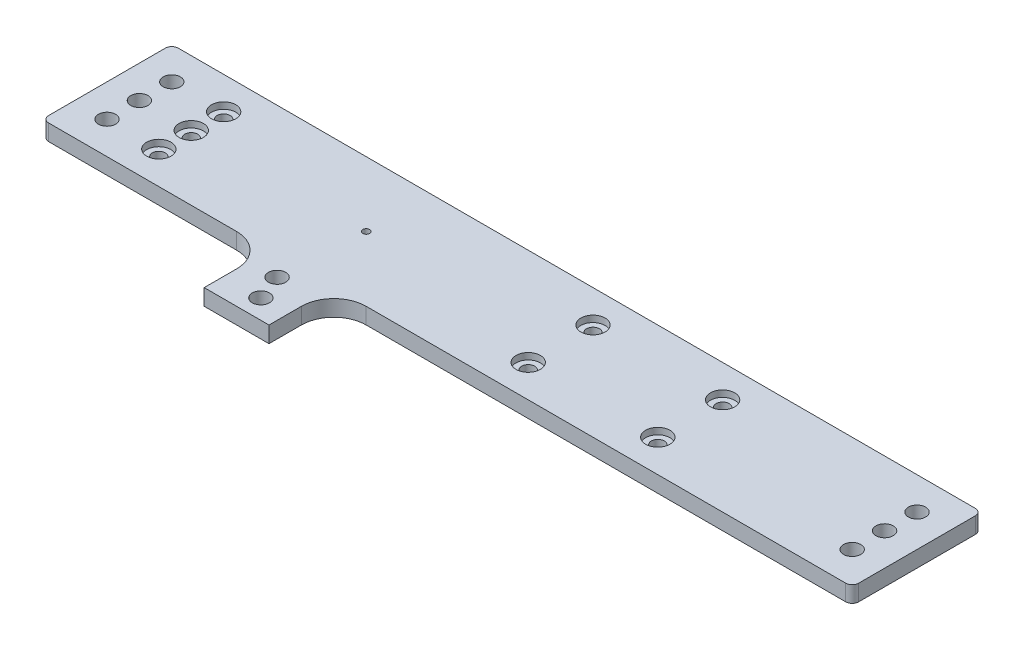
SolidWorks part; units mm, degrees
material "6061-T6 (SS)"
ref_plane "Front" through (0, 0, 0) normal (0, 0, 1) x (1, 0, 0)
ref_plane "Top" through (0, 0, 0) normal (0, 1, 0) x (1, 0, 0)
ref_plane "Right" through (0, 0, 0) normal (1, 0, 0) x (0, 0, -1)
sketch "Sketch1" plane through (0, 0, 0) normal (0, 1, 0) x (1, 0, 0)
  line L1 (-158.75, -25.4) -> (158.75, -25.4)
  line L2 (-158.75, -25.4) -> (-158.75, 25.4)
  line L3 (-158.75, 25.4) -> (158.75, 25.4)
  line L4 (158.75, -25.4) -> (158.75, 25.4)
  line L5 (-158.75, -25.4) -> (158.75, 25.4) construction
  line L6 (-158.75, 25.4) -> (158.75, -25.4) construction
  point P0 (0, 0)
  dimension "D1" = 50.8
  dimension "D2" = 317.5
extrude "Boss-Extrude1" add sketch "Sketch1" along normal blind 6.35
hole_wizard "CBORE for #10 Socket Head Cap Screw1" positions "Sketch2" profile "Sketch4" counterbore size "#10" standard "ANSI Inch" end condition through all
sketch "Sketch2" plane through (0, 6.35, 0) normal (0, 1, 0) x (1, 0, 0)
  line L2 (158.75, 25.4) -> (-158.75, 25.4) construction
  line L6 (-158.75, -25.4) -> (158.75, -25.4) construction
  line L8 (-158.75, 25.4) -> (-158.75, -25.4) construction
  line L12 (158.75, -25.4) -> (158.75, 25.4) construction
  line L15 (19.05, 12.7) -> (19.05, 25.4) construction
  line L17 (19.05, -12.7) -> (19.05, -25.4) construction
  line L18 (-125.73, -25.4) -> (-125.73, -12.7) construction
  line L20 (-125.73, 0) -> (-125.73, 12.7) construction
  line L21 (-125.73, 12.7) -> (-125.73, 25.4) construction
  line L22 (-125.73, 0) -> (-125.73, -12.7) construction
  point P64 (19.05, 12.7)
  point P66 (69.85, 12.7)
  point P68 (19.05, -12.7)
  point P70 (69.85, -12.7)
  point P92 (-125.73, 12.7)
  point P94 (-125.73, 0)
  point P102 (-125.73, -12.7)
  dimension "D2" = 50.8
  dimension "D3" = 25.4
  dimension "D4" = 88.9
  dimension "D5" = 33.02
sketch "Sketch4" plane through (-125.73, 6.35, 12.7) normal (1, 0, 0) x (0, 0, 1)
  line L0 (0, 0) -> (0, 6.35)
  line L1 (0, 6.35) -> (2.5527, 6.35)
  line L3 (2.5527, 6.35) -> (2.5527, 2.54)
  line L4 (2.5527, 2.54) -> (4.7625, 2.54)
  line L5 (4.7625, 2.54) -> (4.7625, 0)
  line L7 (4.7625, 0) -> (0, 0)
  line L11 (0, -6.35) -> (0, 107.95) construction
  dimension "Thru Hole Dia." = 5.1054
  dimension "Thru Hole Depth" = 6.35
  dimension "C'Bore Dia." = 9.525
  dimension "C'Bore Depth" = 2.54
sketch "Sketch7" plane through (0, 0, 0) normal (0, -1, 0) x (1, 0, 0)
  line L0 (-146.05, 25.4) -> (-146.05, 12.7) construction
  line L1 (-158.75, 25.4) -> (158.75, 25.4) construction
  line L2 (-146.05, 12.7) -> (-146.05, 0) construction
  line L3 (-146.05, 0) -> (-146.05, -12.7) construction
  line L4 (-146.05, -12.7) -> (-146.05, -25.4) construction
  line L5 (158.75, -25.4) -> (-158.75, -25.4) construction
  line L7 (-158.75, -25.4) -> (-158.75, 25.4) construction
  line L8 (146.05, 25.4) -> (146.05, 12.7) construction
  line L9 (146.05, 12.7) -> (146.05, 0) construction
  line L10 (146.05, 0) -> (146.05, -12.7) construction
  line L11 (146.05, -12.7) -> (146.05, -25.4) construction
  line L13 (158.75, 25.4) -> (158.75, -25.4) construction
  point P0 (-146.05, 12.7)
  point P2 (-146.05, 0)
  point P4 (-146.05, -12.7)
  point P6 (146.05, 12.7)
  point P8 (146.05, 0)
  point P10 (146.05, -12.7)
  dimension "D1" = 12.7
  dimension "D2" = 12.7
hole_wizard "1/4 Clearance Hole2" positions "Sketch7" profile "Sketch6" hole size "1/4" standard "ANSI Inch" end condition through all
sketch "Sketch6" plane through (-146.05, 0, 12.7) normal (1, 0, 0) x (0, 0, -1)
  line L0 (0, 0) -> (0, 6.35)
  line L1 (0, 6.35) -> (3.3782, 6.35)
  line L2 (3.3782, 6.35) -> (3.3782, 0)
  line L5 (3.3782, 0) -> (0, 0)
  line L11 (0, -6.35) -> (0, 107.95) construction
  dimension "Thru Hole Dia." = 6.7564
  dimension "Thru Hole Depth" = 6.35
sketch "Sketch10" plane through (0, 0, 0) normal (0, -1, 0) x (-1, 0, 0)
  line L0 (158.75, 25.4) -> (158.75, -25.4) construction
  point P0 (57.15, 0)
  dimension "D1" = 101.6
hole_wizard "#6-32 Tapped Hole1" positions "Sketch10" profile "Sketch9" tap size "#6-32" standard "ANSI Inch" end condition through all
sketch "Sketch9" plane through (-57.15, 0, 0) normal (1, 0, 0) x (0, 0, -1)
  line L0 (0, 0) -> (0, 6.35)
  line L1 (0, 6.35) -> (1.3525, 6.35)
  line L2 (1.3525, 6.35) -> (1.3525, 0)
  line L5 (1.3525, 0) -> (0, 0)
  line L11 (0, -6.35) -> (0, 107.95) construction
  dimension "Thru Tap Drill Dia." = 2.7051
  dimension "Thru Tap Drill Depth" = 6.35
cosmetic thread "Hole Thread1" parameters "D2"=3.5052
sketch "Sketch11" plane through (0, 0, 0) normal (0, -1, 0) x (1, 0, 0)
  line L0 (158.75, -25.4) -> (-158.75, -25.4) construction
  line L1 (-70.0118, -25.4) -> (-48.1024, -25.4)
  line L2 (-70.0118, -25.4) -> (-70.0118, -45.81)
  line L3 (-70.0118, -45.81) -> (-48.1024, -45.81)
  line L4 (-48.1024, -25.4) -> (-48.1024, -45.81)
extrude "Boss-Extrude2" [suppressed] add sketch "Sketch11" against normal up to surface (6.35 mm away) up to face at (-57.15, 6.35, -1.3526)
sketch "Sketch12" plane through (0, 6.35, 0) normal (0, 1, 0) x (1, 0, 0)
  line L0 (-158.75, -25.4) -> (158.75, -25.4) construction
  line L1 (-69.85, -25.4) -> (-44.45, -25.4)
  line L2 (-69.85, -25.4) -> (-69.85, -50.8)
  line L3 (-69.85, -50.8) -> (-44.45, -50.8)
  line L4 (-44.45, -25.4) -> (-44.45, -50.8)
  line L5 (-158.75, 25.4) -> (-158.75, -25.4) construction
  dimension "D1" = 88.9
  dimension "D2" = 25.4
  dimension "D3" = 25.4
extrude "Boss-Extrude3" add sketch "Sketch12" against normal up to surface (6.35 mm away) up to face at (-57.15, 0, -1.3526)
sketch "Sketch15" plane through (0, 0, 0) normal (0, -1, 0) x (-1, 0, 0)
  point P0 (55.245, -43.18)
  point P3 (59.055, -33.02)
hole_wizard "1/4 Clearance Hole1" positions "Sketch15" profile "Sketch14" hole size "1/4" standard "ANSI Inch" end condition through all
sketch "Sketch14" plane through (-55.245, 0, 43.18) normal (1, 0, 0) x (0, 0, -1)
  line L0 (0, 0) -> (0, 6.35)
  line L1 (0, 6.35) -> (3.3782, 6.35)
  line L2 (3.3782, 6.35) -> (3.3782, 0)
  line L5 (3.3782, 0) -> (0, 0)
  line L11 (0, -6.35) -> (0, 107.95) construction
  dimension "Thru Hole Dia." = 6.7564
  dimension "Thru Hole Depth" = 6.35
fillet "Fillet1" radius 12.7 2 edges at (-69.85, 3.175, 25.4) (-44.45, 3.175, 25.4)
fillet "Fillet2" radius 2.54 4 edges at (158.75, 3.175, 25.4) (158.75, 3.175, -25.4) (-158.75, 3.175, -25.4) (-158.75, 3.175, 25.4)
